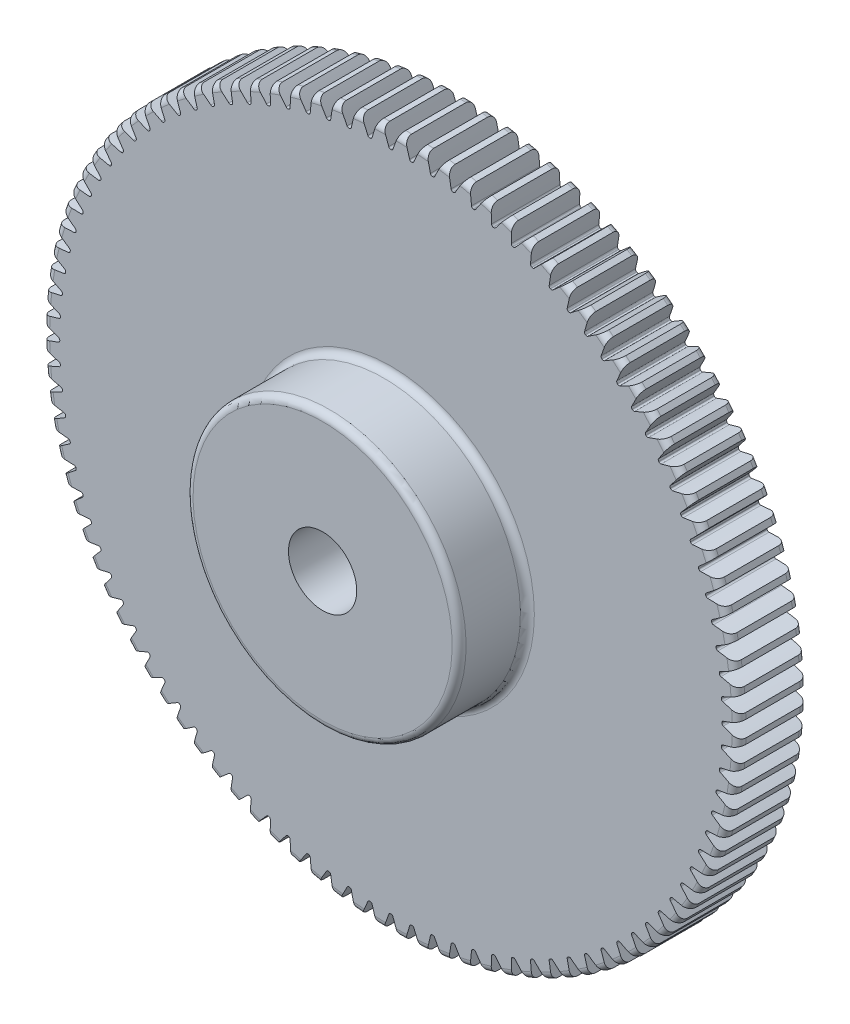
SolidWorks part; units mm, degrees
ref_plane "Front Plane" through (0, 0, 0) normal (0, 0, 1) x (1, 0, 0)
ref_plane "Top Plane" through (0, 0, 0) normal (0, 1, 0) x (1, 0, 0)
ref_plane "Right Plane" through (0, 0, 0) normal (1, 0, 0) x (0, 0, -1)
sketch "Sketch1" plane through (0, 0, 0) normal (0, 0, 1) x (1, 0, 0)
  line L0 (-1270, 0) -> (1270, 0) construction
  circle A0 centre (0, 0) radius 51 construction
  circle A1 centre (0, 0) radius 50 construction
  circle A2 centre (0, 0) radius 48.5 construction
  circle A3 centre (0, 0) radius 20 construction
  circle A4 centre (0, 0) radius 5 construction
  dimension "D2" = 1
  dimension "D3" = 2.5
  dimension "D1" = 2.5
sketch "Sketch2" plane through (0, 0, 0) normal (1, 0, 0) x (0, 0, -1)
  line L0 (0, 0) -> (-10, 0) construction
  line L1 (-10, 0) -> (-20, 0) construction
  dimension "Overall Width" = 20
  dimension "Face Width" = 10
sketch "Sketch4" plane through (0, 0, 0) normal (1, 0, 0) x (0, 0, -1)
  line L0 (-20, 5) -> (-20, 20)
  line L1 (-20, 20) -> (-10, 20)
  line L2 (-10, 20) -> (-10, 51)
  line L3 (-10, 51) -> (0, 51)
  line L4 (0, 51) -> (0, 5)
  line L5 (-10, 20) -> (-10, 0) construction
  line L6 (0, 51) -> (0, -51) construction
  line L7 (-10, 20) -> (0, 20) construction
  line L12 (-20, 5) -> (0, 5)
revolve "Revolve1" add sketch "Sketch4" angle 360 about L1
fillet "Fillet2" radius 1.02 4 edges at (0, 20, 20) (0, 20, 10) (0, 51, 10) (0, 51, 0)
sketch "Sketch7" plane through (0, 0, 10) normal (0, 0, 1) x (1, 0, 0)
  line L0 (0, 0) -> (0, 51) construction
  line L1 (0.7854, 49.9938) -> (1.1645, 50.9867) construction
  line L3 (1.6019, 50.9748) -> (1.5705, 49.9753) construction
  line L4 (1.5705, 49.9753) -> (1.5234, 48.4761) construction
  line L5 (0, 0) -> (1.5234, 48.4761) construction
  line L6 (0.7854, 49.9938) -> (0, 0) construction
  line L7 (0.7854, 49.9938) -> (0.8011, 50.9937) construction
  line L8 (0.7854, 49.9938) -> (0, 0) construction
  circle A0 centre (0, 0) radius 51 construction
  arc A1 (-0.0286, 48.5) -> (0.0286, 48.5) centre (0, 0) cw
  circle A2 centre (0, 0) radius 48.5 construction
  arc A3 (-0.7854, 49.9938) -> (0.7854, 49.9938) centre (0, 0) cw construction
  circle A4 centre (0, 0) radius 50 construction
  arc A5 (2.0272, 50.9597) -> (1.1766, 50.9864) centre (0, 0) ccw construction
  arc A6 (0.7854, 49.9938) -> (2.3553, 49.9445) centre (0, 0) cw construction
  arc A7 (-1.1766, 50.9864) -> (1.1766, 50.9864) centre (0, 0) cw
  arc A8 (0.3119, 48.7007) -> (1.1766, 50.9864) centre (47.4956, 32.1569) cw
  arc A9 (-0.3119, 48.7007) -> (-1.1766, 50.9864) centre (-47.4956, 32.1569) ccw
  arc A10 (-0.0286, 48.5) -> (-0.3119, 48.7007) centre (-0.0288, 48.8) cw
  arc A11 (0.0286, 48.5) -> (0.3119, 48.7007) centre (0.0288, 48.8) ccw
  point P26 (-0.2418, 48.4994)
  point P29 (0.2418, 48.4994)
  dimension "D4" = 0.3
  dimension "D5" = 50
  dimension "D3" = 20
  dimension "D1" = 3.1416
  dimension "D2" = 1.5708
extrude "Cut-Extrude2" cut sketch "Sketch7" against normal through all
pattern_circular "CirPattern1" count 100 over 360 about axis through (0, 0, 20) along (0, 0, -1) of "Cut-Extrude2"
equation "\"D1@Sketch1\"=2.5*(\"Pitch Dia.@Sketch1\"/\"Number of Teeth@Sketch1\")"
equation "\"D1@CirPattern1\"=\"Number of Teeth@Sketch1\""
equation "\"D1@Fillet2\"=\"OD@Sketch1\"*.01"
equation "\"D1@Sketch7\"=3.14159*(\"Pitch Dia.@Sketch1\"/\"Number of Teeth@Sketch1\")"
equation "\"D2@Sketch7\"=\"D1@Sketch7\"/2"
equation "\"D4@Sketch7\"=\"D1@Sketch7\"*.0955"
equation "\"D5@Sketch7\"=\"Pitch Dia.@Sketch1\"/2"
